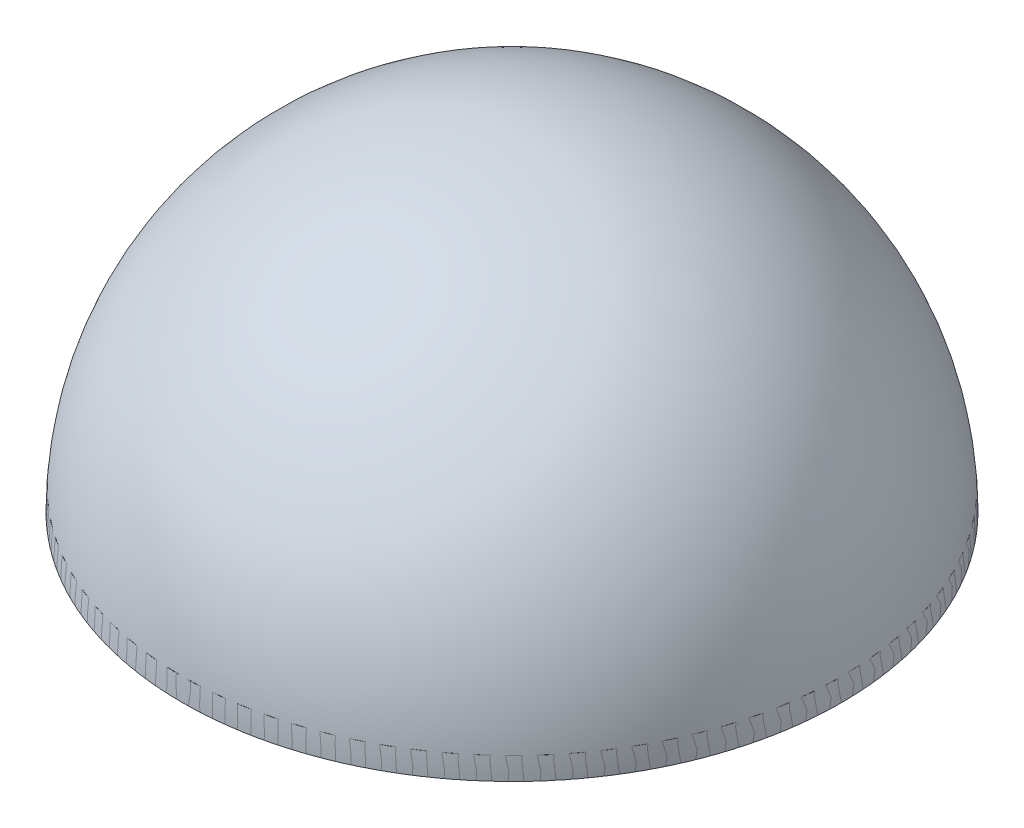
SolidWorks part; units mm, degrees
ref_plane "Front Plane" through (0, 0, 0) normal (0, 0, 1) x (1, 0, 0)
ref_plane "Top Plane" through (0, 0, 0) normal (0, 1, 0) x (1, 0, 0)
ref_plane "Right Plane" through (0, 0, 0) normal (1, 0, 0) x (0, 0, -1)
ref_axis "X-Axis" through (-82.5, 0, 0) along (1, 0, 0)
ref_axis "Z-Axis" through (0, 77.3482, 0) along (0, -1, 0)
ref_axis "Y-Axis" through (0, 0, 82.5) along (0, 0, -1)
sketch3d "Construction lines"
  line L0 (0, 0, 82.5) -> (0, 0, -82.5) construction
  circle A0 centre (0, 0, 0) radius 75 construction
  circle A1 centre (0, 0, 0) radius 71 construction
  circle A2 centre (0, 0, 0) radius 71 construction
  circle A3 centre (0, 0, 0) radius 75 construction
  circle A4 centre (0, 0, 0.6198) radius 75 construction
  circle A5 centre (0, 0, 0) radius 71 construction
  point P2 (0, 75, 0)
  point P5 (0, 71, 0)
  point P7 (0, 0, 71)
  point P10 (0, 0, 75)
  point P12 (75, 0, 0.6198)
  point P16 (71, 0, 0)
  point P18 (0, 0, 0)
sketch "Sketch9" plane through (0, 0, 0) normal (0, 1, 0) x (1, 0, 0)
  line L0 (0, 75) -> (0, 71)
  line L1 (0, -71) -> (0, -75)
  arc A0 (0, 75) -> (0, -75) centre (0, 0) ccw
  arc A1 (0, 71) -> (0, -71) centre (0, 0) ccw
  dimension "D1" = 75
  dimension "D2" = 71
revolve "Shell" add sketch "Sketch9" angle 180 about L0 reverse direction yes
sketch "Sketch4" plane through (0, 0, 0) normal (0, 0, 1) x (1, 0, 0)
  line L0 (-75, 0) -> (-71, 0)
  line L1 (-70.8237, 5) -> (-74.8331, 5)
  line L2 (0, 0) -> (0, 10) construction
  arc A0 (-74.8331, 5) -> (-75, 0) centre (0, 0) ccw
  arc A1 (-70.8237, 5) -> (-71, 0) centre (0, 0) ccw
  dimension "D1" = 75
  dimension "D2" = 71
  dimension "D3" = 5
revolve "Base" add sketch "Sketch4" angle 360 about L2
equation "\"wall_thickness\"= 1"
equation "\"radius\"= 75mm"
equation "\"shell_thickness\"= 4mm"
equation "\"D1@Sketch9\"=\"radius\""
equation "\"D2@Sketch9\"=\"radius\"-\"shell_thickness\""
equation "\"D1@Sketch4\"=\"radius\""
equation "\"D2@Sketch4\"=\"radius\"-\"shell_thickness\""
equation "\"base_height\"= 5mm"
equation "\"D3@Sketch4\"=\"base_height\""
equation "\"edge_scribed\"= \"radius\" * 1.0044063878192154002"
